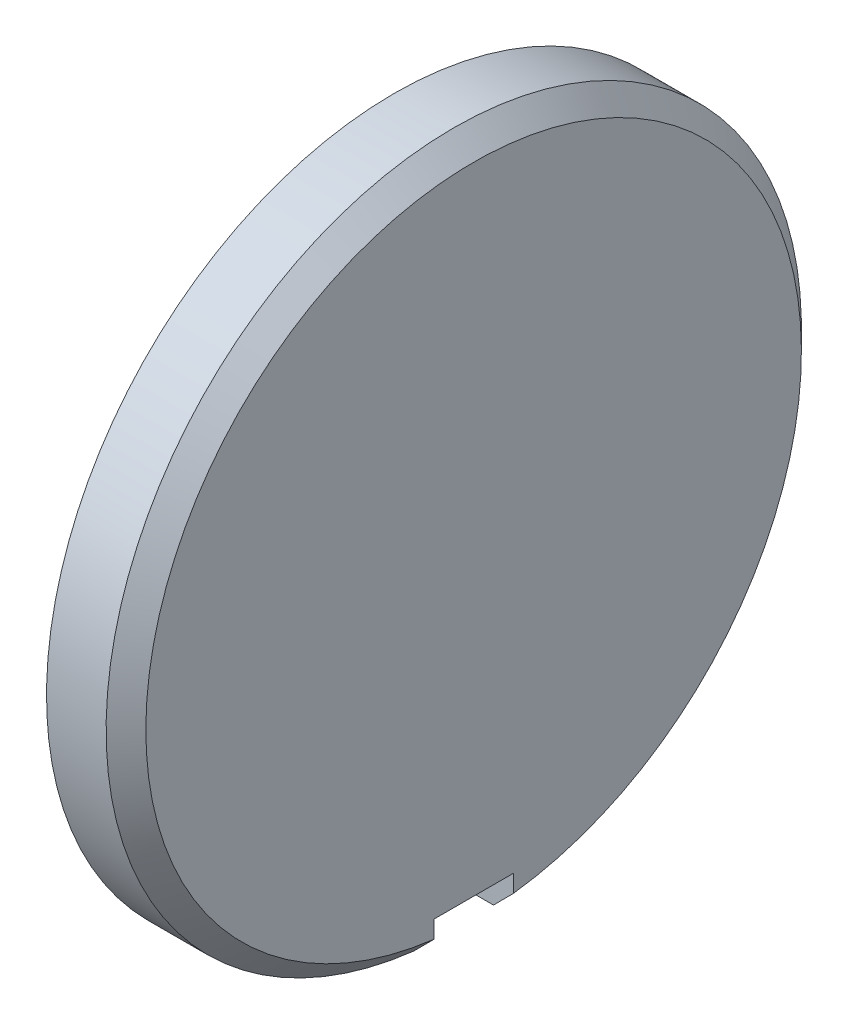
SolidWorks part; units mm, degrees
ref_plane "Front Plane" through (0, 0, 0) normal (0, 0, 1) x (1, 0, 0)
ref_plane "Top Plane" through (0, 0, 0) normal (0, 1, 0) x (1, 0, 0)
ref_plane "Right Plane" through (0, 0, 0) normal (1, 0, 0) x (0, 0, -1)
ref_plane "Plane1" through (0, 0, -52) normal (0, 0, 1) x (1, 0, 0)
sketch "Sketch1" plane through (0, 0, -52) normal (0, 0, 1) x (1, 0, 0)
  line L0 (77.8, -65) -> (90.6, -65) construction
  line L1 (82.8, -62.7) -> (84, -62.7)
  line L2 (84, -62.7) -> (84, -65)
  line L3 (84, -65) -> (85.6, -65)
  line L4 (85.6, -65) -> (85.6, -58.4)
  line L5 (85.6, -58.4) -> (85.2, -58)
  line L6 (85.2, -58) -> (84, -58)
  line L7 (84, -58) -> (84, -62)
  line L8 (84, -62) -> (82.8, -62)
  line L9 (82.8, -62) -> (82.8, -62.7)
revolve "Revolve1" add sketch "Sketch1" angle 360 about L0
sketch "Sketch2" plane through (0, 0, 0) normal (0, 0, 1) x (1, 0, 0)
  line L1 (82.7, -65.4) -> (83.98, -65.4)
  line L2 (82.7, -65.4) -> (82.7, -64.6)
  line L3 (82.7, -64.6) -> (83.98, -64.6)
  line L4 (83.98, -65.4) -> (83.98, -64.6)
extrude "Boss-Extrude1" add sketch "Sketch2" along normal blind 6.4 from offset 55.2 separate body offset against normal yes
combine bodies "Combine1" operation type subtract main body 101 bodies to subtract 102
sketch "Sketch3" plane through (0, 0, 0) normal (0, 0, 1) x (1, 0, 0)
  line L1 (82.7, -68.2) -> (83.98, -68.2)
  line L2 (82.7, -68.2) -> (82.7, -61.8)
  line L3 (82.7, -61.8) -> (83.98, -61.8)
  line L4 (83.98, -68.2) -> (83.98, -61.8)
extrude "Boss-Extrude2" add sketch "Sketch3" along normal blind 0.8 from offset 52.4 separate body offset against normal yes
combine bodies "Combine2" operation type subtract main body 103 bodies to subtract 104
sketch "Sketch4" plane through (0, 0, 0) normal (0, 0, 1) x (1, 0, 0)
  line L1 (83.9, -72.1) -> (85.7, -72.1)
  line L2 (83.9, -72.1) -> (83.9, -71.2)
  line L3 (83.9, -71.2) -> (85.7, -71.2)
  line L4 (85.7, -72.1) -> (85.7, -71.2)
extrude "Boss-Extrude3" add sketch "Sketch4" along normal blind 1.6 from offset 52.8 separate body offset against normal yes
combine bodies "Combine3" operation type subtract main body 105 bodies to subtract 106
